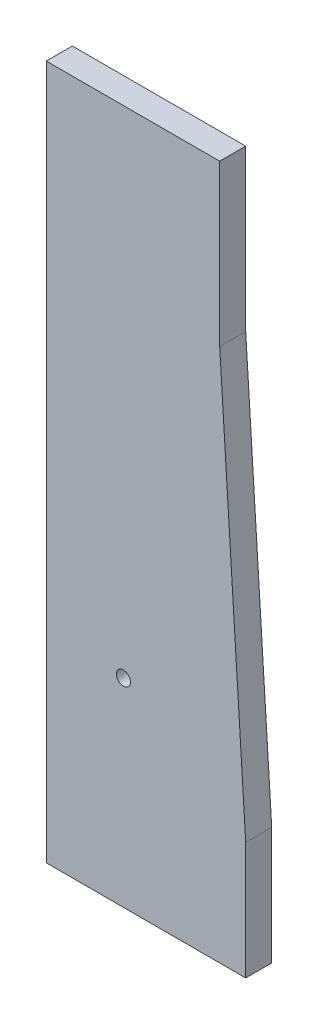
SolidWorks part; units mm, degrees
material "MDF"
ref_plane "Front Plane" through (0, 0, 0) normal (0, 0, 1) x (1, 0, 0)
ref_plane "Top Plane" through (0, 0, 0) normal (0, 1, 0) x (1, 0, 0)
ref_plane "Right Plane" through (0, 0, 0) normal (1, 0, 0) x (0, 0, -1)
sketch "Sketch1" plane through (0, 0, 0) normal (0, 0, 1) x (1, 0, 0)
  line L0 (82.0395, -5024.8784) -> (82.0395, -5533.4155)
  line L1 (82.0395, -5024.8784) -> (82.0395, -5464.9635) construction
  line L8 (-209.0395, -5024.8784) -> (-209.0395, -5142.5528)
  line L11 (-228.0888, -5533.4155) -> (228.0888, -5533.4155)
  line L14 (209.0395, -5142.5528) -> (209.0395, -5024.8784)
  line L15 (209.0395, -5024.8784) -> (-209.0395, -5024.8784)
  line L22 (209.0395, -5142.5528) -> (209.0395, -5024.8784)
  line L23 (209.0395, -5024.8784) -> (82.0395, -5024.8784)
  line L106 (82.0395, -5533.4155) -> (228.0888, -5533.4155)
  line L119 (-209.0395, -5142.5528) -> (-228.0888, -5447.3417)
  line L120 (-228.0888, -5447.3417) -> (-228.0888, -5533.4155)
  line L121 (228.0888, -5533.4155) -> (228.0888, -5447.3417)
  line L122 (228.0888, -5533.4155) -> (228.0888, -5447.3417)
  line L123 (228.0888, -5447.3417) -> (209.0395, -5142.5528)
  line L124 (228.0888, -5447.3417) -> (209.0395, -5142.5528)
  dimension "D1" = 0
extrude "Boss-Extrude1" add sketch "Sketch1" along normal blind 19.05
hole_wizard "3/8 Clearance Hole1" positions "Sketch2" profile "Sketch4" hole size "3/8" standard "ANSI Inch" end condition through all
sketch "Sketch2" plane through (0, 0, 19.05) normal (0, 0, 1) x (1, 0, 0)
  point P9 (138.551, -5387.9638)
  point P13 (138.551, -5387.9638)
sketch "Sketch4" plane through (138.551, -5387.9638, 19.05) normal (1, 0, 0) x (0, -1, 0)
  line L0 (0, 0) -> (0, 19.05)
  line L1 (0, 19.05) -> (5.1587, 19.05)
  line L2 (5.1587, 19.05) -> (5.1587, 0)
  line L5 (5.1587, 0) -> (0, 0)
  line L11 (0, -6.35) -> (0, 107.95) construction
  dimension "Thru Hole Dia." = 10.3175
  dimension "Thru Hole Depth" = 19.05
